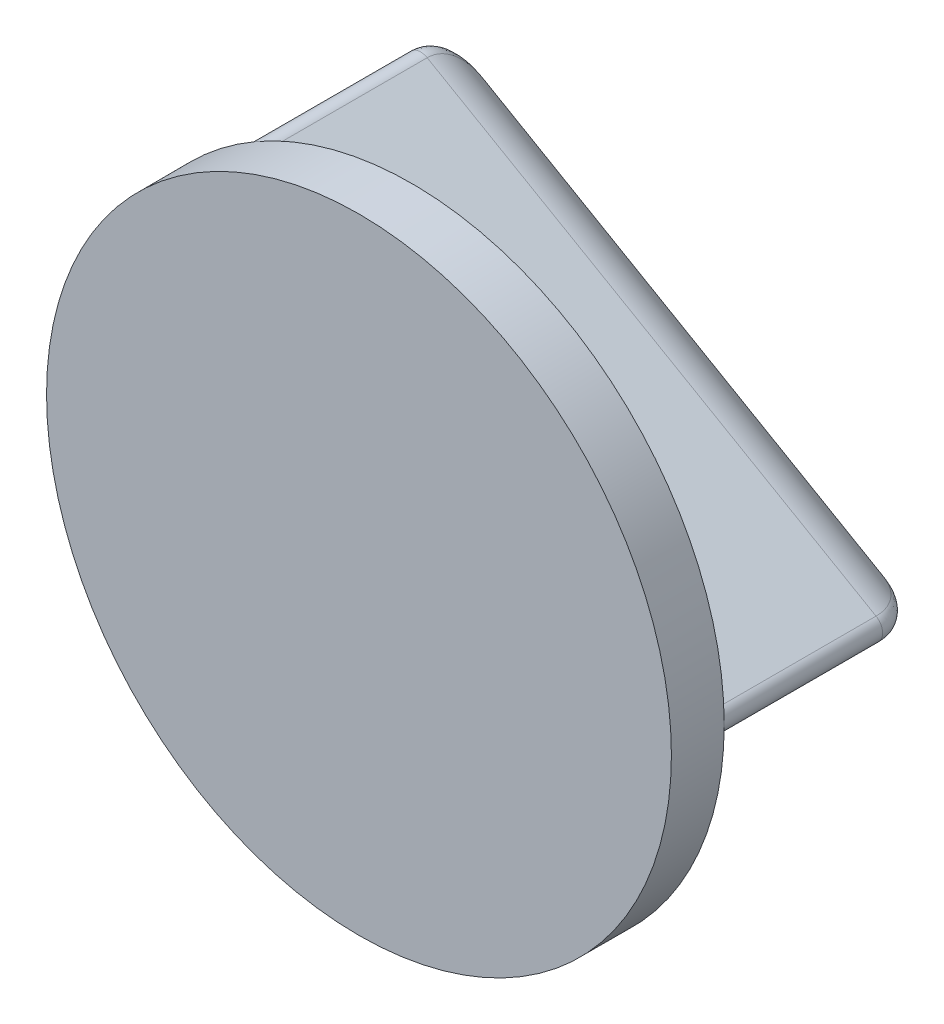
SolidWorks part; units mm, degrees
ref_plane "Front Plane" through (0, 0, 0) normal (0, 0, 1) x (1, 0, 0)
ref_plane "Top Plane" through (0, 0, 0) normal (0, 1, 0) x (1, 0, 0)
ref_plane "Right Plane" through (0, 0, 0) normal (1, 0, 0) x (0, 0, -1)
sketch "Sketch1" plane through (0, 0, 0) normal (0, 0, 1) x (1, 0, 0)
  line L0 (6.6029, 0.042) -> (-2.8971, 0.042) construction
  line L1 (-2.6471, 5.3825) -> (2.1029, -2.8448) construction
  line L2 (-2.6471, -5.2985) -> (2.1029, 2.9287) construction
  line L3 (-2.6471, 4.9495) -> (-2.6471, -4.8655)
  line L4 (-2.2721, 5.166) -> (6.2279, 0.2585)
  line L5 (-2.2721, -5.082) -> (6.2279, -0.1745)
  line L34 (6.3529, -0.391) -> (-2.1471, -5.2985) construction
  line L35 (-2.1471, 5.3825) -> (6.3529, 0.475) construction
  line L36 (-2.8971, -4.8655) -> (-2.8971, 4.9495) construction
  arc A0 (-2.6471, 4.9495) -> (-2.2721, 5.166) centre (-2.3971, 4.9495) cw
  arc A1 (6.2279, 0.2585) -> (6.2279, -0.1745) centre (6.1029, 0.042) cw
  arc A2 (-2.8971, -4.8655) -> (-2.1471, -5.2985) centre (-2.3971, -4.8655) ccw construction
  arc A3 (-2.6471, -4.8655) -> (-2.2721, -5.082) centre (-2.3971, -4.8655) ccw
  arc A7 (6.3529, -0.391) -> (6.3529, 0.475) centre (6.1029, 0.042) ccw construction
  arc A8 (-2.8971, 4.9495) -> (-2.1471, 5.3825) centre (-2.3971, 4.9495) cw construction
  arc A9 (-2.1471, -5.2985) -> (-2.8971, -4.8655) centre (-2.3971, -4.8655) cw construction
  point P2 (0.4362, 0.042)
  point P15 (-2.6471, 0.042)
extrude "Boss-Extrude2" add sketch "Sketch1" along normal blind 5
sketch "Sketch4" plane through (0, 0, 5) normal (0, 0, 1) x (1, 0, 0)
  line L0 (-2.5221, 5.166) -> (1.9779, -2.6283) construction
  line L1 (-2.2721, -5.082) -> (6.2279, -0.1745) construction
  line L2 (-2.6471, 0.042) -> (6.3529, 0.042) construction
  line L3 (-2.6471, 4.9495) -> (-2.6471, -4.8655) construction
  arc A0 (-2.2721, 5.166) -> (-2.6471, 4.9495) centre (-2.3971, 4.9495) ccw construction
  arc A1 (6.2279, -0.1745) -> (6.2279, 0.2585) centre (6.1029, 0.042) ccw construction
  circle A2 centre (0.4362, 0.042) radius 5.9167
  point P14 (0.4362, 0.042)
extrude "Boss-Extrude3" add sketch "Sketch4" against normal blind 1
fillet "Fillet1" radius 1 6 edges at (6.3529, 0.042, 0) (1.9779, -2.6283, 0) (-2.5221, -5.082, 0) (-2.6471, 0.042, 0) (-2.5221, 5.166, 0) (1.9779, 2.7122, 0)
ref_plane "Plan1" through (-12.6471, 0, 0) normal (-1, 0, 0) x (0, 0, 1)
sketch "Esquisse1" plane through (-12.6471, 0, 0) normal (-1, 0, 0) x (0, 0, 1)
  line L0 (0, 0) -> (0, -5.4671) construction
